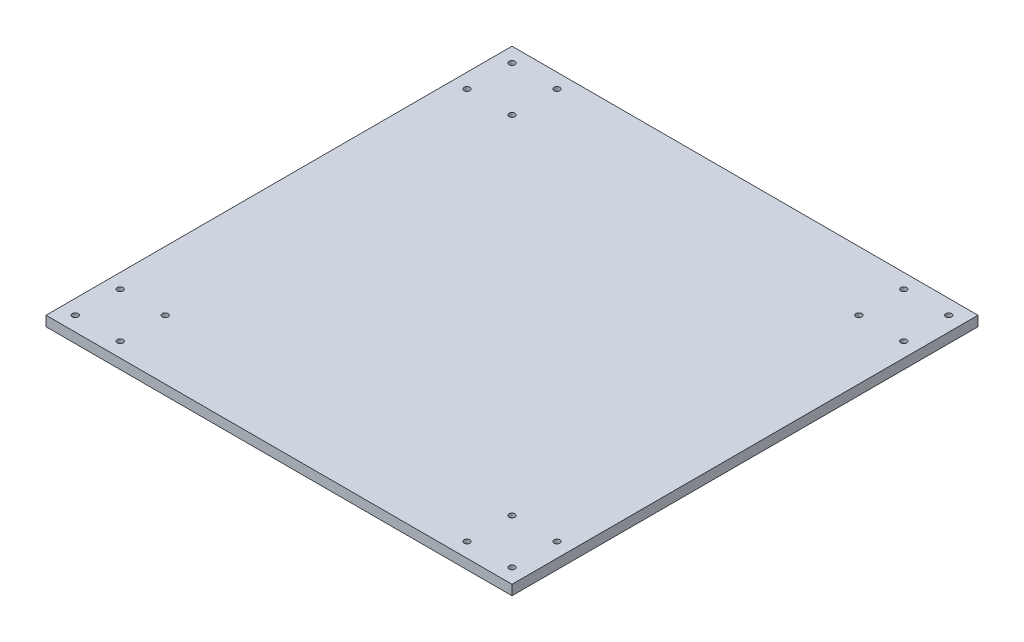
SolidWorks part; units mm, degrees
ref_plane "Front Plane" through (0, 0, 0) normal (0, 0, 1) x (1, 0, 0)
ref_plane "Top Plane" through (0, 0, 0) normal (0, 1, 0) x (1, 0, 0)
ref_plane "Right Plane" through (0, 0, 0) normal (1, 0, 0) x (0, 0, -1)
sketch "Sketch1" plane through (0, 0, 0) normal (0, 1, 0) x (1, 0, 0)
  line L0 (104.0003, -130.9497) -> (130.9497, -130.9497) construction
  line L1 (-139.7, -139.7) -> (139.7, -139.7)
  line L2 (-139.7, -139.7) -> (-139.7, 139.7)
  line L3 (-139.7, 139.7) -> (139.7, 139.7)
  line L4 (139.7, -139.7) -> (139.7, 139.7)
  line L5 (-139.7, -139.7) -> (139.7, 139.7) construction
  line L6 (-139.7, 139.7) -> (139.7, -139.7) construction
  line L7 (-117.475, 117.475) -> (117.475, 117.475) construction
  line L8 (-117.475, 117.475) -> (-117.475, -117.475) construction
  line L9 (-117.475, -117.475) -> (117.475, -117.475) construction
  line L10 (117.475, 117.475) -> (117.475, -117.475) construction
  line L11 (-117.475, 117.475) -> (117.475, -117.475) construction
  line L12 (-117.475, -117.475) -> (117.475, 117.475) construction
  line L13 (-130.9497, -130.9497) -> (-104.0003, -130.9497) construction
  line L14 (-130.9497, -130.9497) -> (-130.9497, -104.0003) construction
  line L15 (-130.9497, -104.0003) -> (-104.0003, -104.0003) construction
  line L16 (-104.0003, -130.9497) -> (-104.0003, -104.0003) construction
  line L17 (-130.9497, -130.9497) -> (-104.0003, -104.0003) construction
  line L18 (-130.9497, -104.0003) -> (-104.0003, -130.9497) construction
  line L19 (104.0003, -130.9497) -> (104.0003, -104.0003) construction
  line L20 (104.0003, -104.0003) -> (130.9497, -104.0003) construction
  line L21 (130.9497, -130.9497) -> (130.9497, -104.0003) construction
  line L22 (104.0003, -130.9497) -> (130.9497, -104.0003) construction
  line L23 (104.0003, -104.0003) -> (130.9497, -130.9497) construction
  line L24 (58.1443, -58.46) -> (85.0937, -85.4094) construction
  line L25 (104.0003, 104.0003) -> (130.9497, 104.0003) construction
  line L26 (104.0003, 104.0003) -> (104.0003, 130.9497) construction
  line L27 (104.0003, 130.9497) -> (130.9497, 130.9497) construction
  line L28 (130.9497, 104.0003) -> (130.9497, 130.9497) construction
  line L29 (104.0003, 104.0003) -> (130.9497, 130.9497) construction
  line L30 (104.0003, 130.9497) -> (130.9497, 104.0003) construction
  line L31 (-130.9497, 104.0003) -> (-104.0003, 104.0003) construction
  line L32 (-130.9497, 104.0003) -> (-130.9497, 130.9497) construction
  line L33 (-130.9497, 130.9497) -> (-104.0003, 130.9497) construction
  line L34 (-104.0003, 104.0003) -> (-104.0003, 130.9497) construction
  line L35 (-130.9497, 104.0003) -> (-104.0003, 130.9497) construction
  line L36 (-130.9497, 130.9497) -> (-104.0003, 104.0003) construction
  circle A0 centre (-130.9497, -130.9497) radius 1.778
  circle A1 centre (-104.0003, -130.9497) radius 1.778
  circle A2 centre (-130.9497, -104.0003) radius 1.778
  circle A3 centre (-104.0003, -104.0003) radius 1.778
  circle A4 centre (104.0003, -130.9497) radius 1.778
  circle A5 centre (130.9497, -130.9497) radius 1.778
  circle A6 centre (104.0003, -104.0003) radius 1.778
  circle A7 centre (130.9497, -104.0003) radius 1.778
  circle A8 centre (104.0003, 104.0003) radius 1.778
  circle A9 centre (130.9497, 104.0003) radius 1.778
  circle A10 centre (104.0003, 130.9497) radius 1.778
  circle A11 centre (130.9497, 130.9497) radius 1.778
  circle A12 centre (-130.9497, 104.0003) radius 1.778
  circle A13 centre (-104.0003, 104.0003) radius 1.778
  circle A14 centre (-130.9497, 130.9497) radius 1.778
  circle A15 centre (-104.0003, 130.9497) radius 1.778
  point P0 (0, 0)
  point P6 (0, 0)
  dimension "D1" = 22.225
extrude "Boss-Extrude1" add sketch "Sketch1" along normal blind 5.9944
